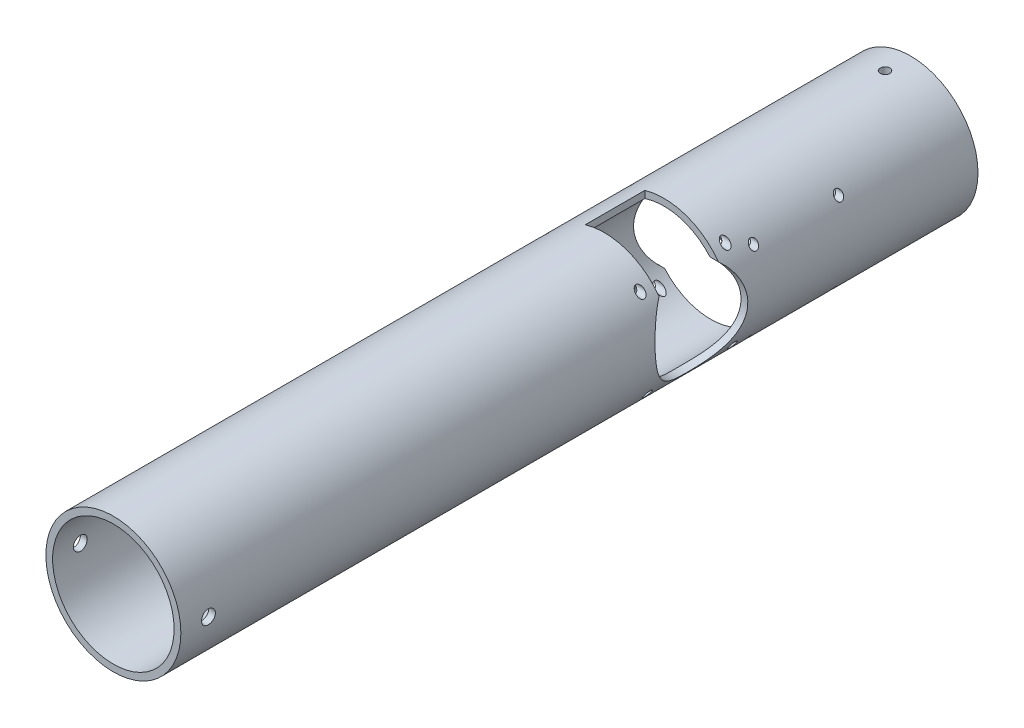
SolidWorks part; units mm, degrees
material "6061 Alloy"
ref_plane "Front Plane" through (0, 0, 0) normal (0, 0, 1) x (1, 0, 0)
ref_plane "Top Plane" through (0, 0, 0) normal (0, 1, 0) x (1, 0, 0)
ref_plane "Right Plane" through (0, 0, 0) normal (1, 0, 0) x (0, 0, -1)
sketch "Sketch1" plane through (0, 0, 0) normal (0, 0, 1) x (1, 0, 0)
  circle A0 centre (0, 0) radius 31.75
  circle A1 centre (0, 0) radius 28.575
  dimension "D1" = 63.5
  dimension "D2" = 57.15
extrude "Boss-Extrude1" add sketch "Sketch1" along normal blind 125 and the other way blind 250 contours A1 | A0 region at (0, 0, 0)
sketch "Sketch2" plane through (0, 0, 0) normal (1, 0, 0) x (0, 0, -1)
  circle A2 centre (170, -2) radius 21.75
  dimension "D1" = 43.5
  dimension "D2" = 170
  dimension "D3" = 2
extrude "Cut-Extrude1" cut sketch "Sketch2" against normal through all
sketch "Sketch3" plane through (0, 0, 0) normal (1, 0, 0) x (0, 0, -1)
  circle A1 centre (120, 2) radius 21.75
  dimension "D1" = 120
  dimension "D2" = 43.5
  dimension "D3" = 2
extrude "Cut-Extrude2" cut sketch "Sketch3" along normal through all
sketch "Sketch5" plane through (0, 0, 0) normal (1, 0, 0) x (0, 0, -1)
  line L1 (184, -12.75) -> (156, -12.75)
  line L2 (184, -12.75) -> (184, -34.75)
  line L3 (184, -34.75) -> (156, -34.75)
  line L4 (156, -12.75) -> (156, -34.75)
  line L5 (184, -12.75) -> (156, -34.75) construction
  line L6 (184, -34.75) -> (156, -12.75) construction
  circle A0 centre (170, -2) radius 21.75 construction
  circle A1 centre (170, -2) radius 21.75 construction
  point P0 (170, -23.75)
  dimension "D1" = 28
  dimension "D2" = 22
  dimension "D3" = 170
extrude "Cut-Extrude4" cut sketch "Sketch5" against normal through all from offset 9
sketch "Sketch6" plane through (0, 0, 0) normal (1, 0, 0) x (0, 0, -1)
  line L1 (106, 34.75) -> (134, 34.75)
  line L2 (106, 34.75) -> (106, 12.75)
  line L3 (106, 12.75) -> (134, 12.75)
  line L4 (134, 34.75) -> (134, 12.75)
  line L5 (106, 34.75) -> (134, 12.75) construction
  line L6 (106, 12.75) -> (134, 34.75) construction
  circle A0 centre (120, 2) radius 21.75 construction
  circle A1 centre (120, 2) radius 21.75 construction
  point P0 (120, 23.75)
  dimension "D1" = 28
  dimension "D2" = 22
  dimension "D3" = 120
extrude "Cut-Extrude5" cut sketch "Sketch6" along normal through all from offset 9 offset against normal yes
sketch "Sketch10" plane through (0, 0, 0) normal (1, 0, 0) x (0, 0, -1)
  line L1 (210, 38) -> (130, 38)
  line L2 (210, 38) -> (210, -42)
  line L3 (210, -42) -> (130, -42)
  line L4 (130, 38) -> (130, -42)
  line L5 (210, 38) -> (130, -42) construction
  line L6 (210, -42) -> (130, 38) construction
  point P0 (170, -2)
  dimension "D1" = 80
  dimension "D2" = 80
sketch "Sketch11" plane through (0, 0, 0) normal (1, 0, 0) x (0, 0, -1)
  line L0 (210, 38) -> (130, -42) construction
  line L1 (210, -42) -> (130, 38) construction
  circle A0 centre (190, 18) radius 2
  circle A1 centre (150, 18) radius 2
  circle A2 centre (150, -22) radius 2
  circle A3 centre (190, -22) radius 2
  dimension "D5" = 4
  dimension "D6" = 4
  dimension "D7" = 4
  dimension "D8" = 4
  dimension "D1" = 20
  dimension "D2" = 20
  dimension "D3" = 20
  dimension "D4" = 20
extrude "Cut-Extrude8" cut sketch "Sketch11" against normal through all both and the other way through all
sketch "Sketch12" plane through (0, 0, 0) normal (1, 0, 0) x (0, 0, -1)
  line L1 (-125, 31.75) -> (-125, -31.75) construction
  circle A0 centre (-136, 0) radius 3.25
  circle A1 centre (-112, 0) radius 3.25
  dimension "D1" = 6.5
  dimension "D2" = 6.5
  dimension "D3" = 24
  dimension "D4" = 13
extrude "Cut-Extrude10" cut sketch "Sketch12" against normal through all both and the other way through all
sketch "Sketch13" plane through (0, 0, 0) normal (0, 1, 0) x (1, 0, 0)
  line L0 (0, -55) -> (0, 55) construction
  line L1 (28.575, 250) -> (-28.575, 250) construction
  circle A0 centre (0, 238) radius 2.25
  dimension "D2" = 4.5
  dimension "D1" = 12
extrude "Cut-Extrude11" cut sketch "Sketch13" against normal through all both and the other way through all
sketch "Sketch14" plane through (0, 0, 0) normal (1, 0, 0) x (0, 0, -1)
  line L1 (95, 27) -> (145, 27)
  line L2 (95, 27) -> (95, -23)
  line L3 (95, -23) -> (145, -23)
  line L4 (145, 27) -> (145, -23)
  line L5 (95, 27) -> (145, -23) construction
  line L6 (95, -23) -> (145, 27) construction
  circle A0 centre (100, 22) radius 2
  circle A1 centre (140, 22) radius 2
  circle A2 centre (140, -18) radius 2
  circle A3 centre (100, -18) radius 2
  point P0 (120, 2)
  dimension "D4" = 4
  dimension "D5" = 4
  dimension "D6" = 4
  dimension "D7" = 4
  dimension "D1" = 50
  dimension "D2" = 50
  dimension "D3" = 20
  dimension "D8" = 20
  dimension "D9" = 20
  dimension "D10" = 20
sketch "Sketch15" plane through (0, 0, 0) normal (1, 0, 0) x (0, 0, -1)
  circle A0 centre (100, 22) radius 2
  circle A1 centre (140, 22) radius 2
  circle A2 centre (140, -18) radius 2
  circle A3 centre (100, -18) radius 2
extrude "Cut-Extrude12" cut sketch "Sketch15" against normal through all and the other way through all
